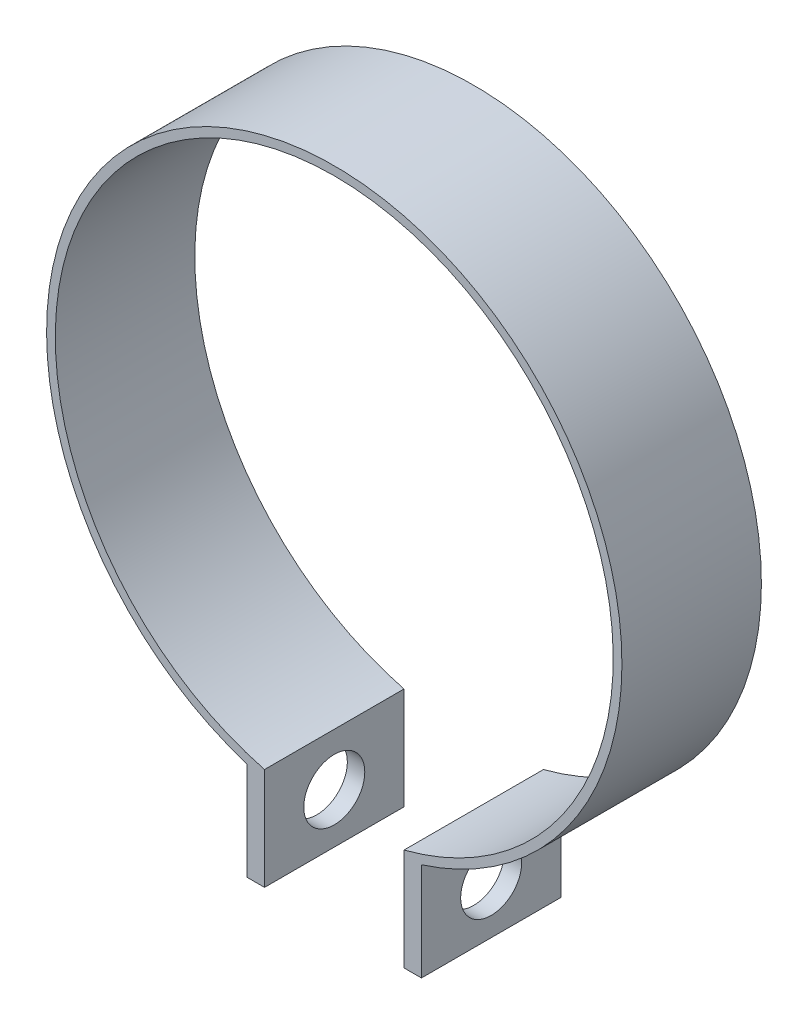
SolidWorks part; units mm, degrees
ref_plane "Alzado" through (0, 0, 0) normal (0, 0, 1) x (1, 0, 0)
ref_plane "Planta" through (0, 0, 0) normal (0, 1, 0) x (1, 0, 0)
ref_plane "Vista lateral" through (0, 0, 0) normal (1, 0, 0) x (0, 0, -1)
sketch "Croquis1" plane through (0, 0, 0) normal (0, 0, 1) x (1, 0, 0)
  line L0 (-4, -15.4919) -> (-4, -21.3482)
  line L6 (-4, -21.3482) -> (-5, -21.3482)
  line L7 (-4, -15.4919) -> (-4, -21.3482)
  line L8 (-5, -15.7242) -> (-5, -21.3482)
  line L9 (4, -15.4919) -> (4, -21.3482)
  line L10 (4, -15.4919) -> (4, -21.3482)
  line L12 (4, -21.3482) -> (5, -21.3482)
  line L13 (5, -15.7242) -> (5, -21.3482)
  arc A0 (4, -15.4919) -> (-4, -15.4919) centre (0, 0) ccw
  arc A1 (5, -15.7242) -> (-5, -15.7242) centre (0, 0) ccw
  dimension "D1" = 32
  dimension "D2" = 33
  dimension "D3" = 8
  dimension "D4" = 1
  dimension "D5" = 1
extrude "Saliente-Extruir1" add sketch "Croquis1" along normal blind 8 contours L13 A1 L8 L6 L0 A0 L9 L12 region at (-4.5021, -18.4201, 0)
sketch "Croquis3" plane through (-4, 0, 0) normal (1, 0, 0) x (0, 0, -1)
  line L0 (-4, -15.4919) -> (-4, -21.3482) construction
  line L1 (-8, -15.4919) -> (0, -15.4919) construction
  line L2 (-8, -21.3482) -> (0, -21.3482) construction
  circle A0 centre (-4, -18.4919) radius 1.75
  dimension "D2" = 3.5
  dimension "D1" = 3
extrude "Cortar-Extruir1" cut sketch "Croquis3" against normal blind 8 and the other way blind 12
